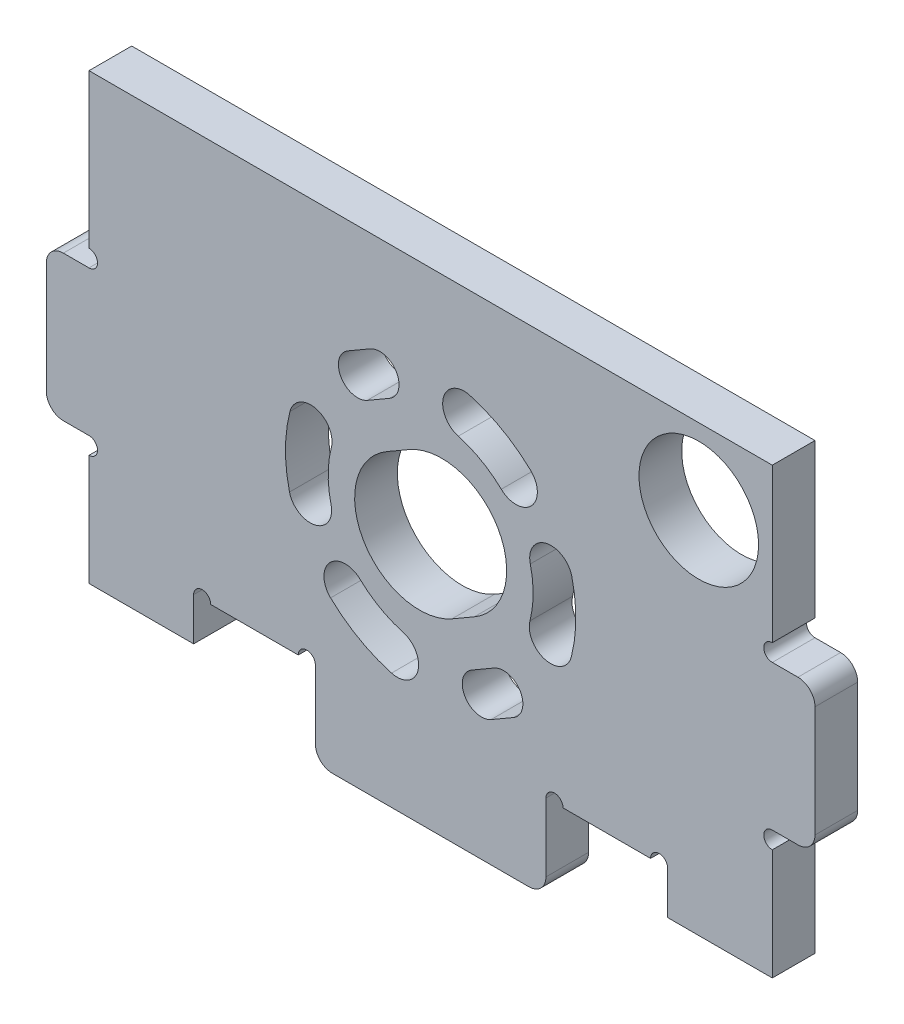
SolidWorks part; units mm, degrees
ref_plane "정면" through (0, 0, 0) normal (0, 0, 1) x (1, 0, 0)
ref_plane "윗면" through (0, 0, 0) normal (0, 1, 0) x (1, 0, 0)
ref_plane "우측면" through (0, 0, 0) normal (1, 0, 0) x (0, 0, -1)
sketch "스케치1" plane through (0, 0, 0) normal (0, 0, 1) x (1, 0, 0)
  line L0 (-3.8971, 23.25) -> (-1.299, 24.75) construction
  line L1 (-42.5981, 51) -> (37.4019, 51)
  line L2 (-42.5981, 51) -> (-42.5981, -1)
  line L3 (-42.5981, -1) -> (37.4019, -1)
  line L4 (37.4019, 51) -> (37.4019, -1)
  line L5 (-7.6971, 29.8318) -> (-5.099, 31.3318)
  line L6 (-0.0971, 16.6682) -> (2.501, 18.1682)
  line L7 (-9.8481, 36.5574) -> (-2.5981, 24) construction
  line L8 (-2.5981, 24) -> (4.6519, 11.4426) construction
  line L9 (-2.5981, 24) -> (4.6519, 36.5574) construction
  line L10 (-2.5981, 24) -> (11.9019, 24) construction
  line L11 (-2.5981, 24) -> (9.9593, 31.25) construction
  arc A0 (-7.6971, 29.8318) -> (-0.0971, 16.6682) centre (-3.8971, 23.25) ccw
  circle A1 centre (-2.5981, 24) radius 14.5 construction
  arc A2 (1.3092, 37.9636) -> (7.3956, 34.506) centre (-2.5981, 24) cw construction
  arc A3 (2.501, 18.1682) -> (-5.099, 31.3318) centre (-1.299, 24.75) ccw
  arc A4 (9.1187, 36.3174) -> (1.9829, 40.3712) centre (-2.5981, 24) ccw
  arc A5 (5.6726, 32.6946) -> (0.6355, 35.5561) centre (-2.5981, 24) ccw
  arc A6 (5.6726, 32.6946) -> (9.1187, 36.3174) centre (7.3956, 34.506) ccw
  arc A7 (1.9829, 40.3712) -> (0.6355, 35.5561) centre (1.3092, 37.9636) ccw
  arc A8 (11.4484, 20.402) -> (11.4972, 27.4018) centre (-2.5981, 24) ccw construction
  arc A9 (13.9275, 27.9883) -> (13.8702, 19.7816) centre (-2.5981, 24) cw
  arc A10 (9.067, 26.8153) -> (9.0266, 21.0223) centre (-2.5981, 24) cw
  arc A11 (9.067, 26.8153) -> (13.9275, 27.9883) centre (11.4972, 27.4018) cw
  arc A12 (13.8702, 19.7816) -> (9.0266, 21.0223) centre (11.4484, 20.402) cw
  arc A13 (-6.5053, 10.0364) -> (-12.5918, 13.494) centre (-2.5981, 24) cw construction
  arc A14 (-14.3148, 11.6826) -> (-7.179, 7.6288) centre (-2.5981, 24) ccw
  arc A15 (-10.8687, 15.3054) -> (-5.8317, 12.4439) centre (-2.5981, 24) ccw
  arc A16 (-10.8687, 15.3054) -> (-14.3148, 11.6826) centre (-12.5918, 13.494) ccw
  arc A17 (-7.179, 7.6288) -> (-5.8317, 12.4439) centre (-6.5053, 10.0364) ccw
  arc A18 (-16.6446, 27.598) -> (-16.6934, 20.5982) centre (-2.5981, 24) ccw construction
  arc A19 (-19.1236, 20.0117) -> (-19.0664, 28.2184) centre (-2.5981, 24) cw
  arc A20 (-14.2632, 21.1847) -> (-14.2228, 26.9777) centre (-2.5981, 24) cw
  arc A21 (-14.2632, 21.1847) -> (-19.1236, 20.0117) centre (-16.6934, 20.5982) cw
  arc A22 (-19.0664, 28.2184) -> (-14.2228, 26.9777) centre (-16.6446, 27.598) cw
  point P3 (-2.5981, 24)
  point P20 (4.5642, 36.6076)
  point P28 (11.9016, 23.8989)
  point P35 (-9.7603, 11.3924)
  point P42 (-17.0977, 24.1011)
  dimension "D1" = 30
  dimension "D2" = 40
  dimension "D8" = 7.6
  dimension "D5" = 29
  dimension "D11" = 2.5
  dimension "D3" = 80
  dimension "D4" = 52
  dimension "D6" = 60
  dimension "D7" = 3
  dimension "D9" = 25
  dimension "D10" = 60
  dimension "D12" = 7
extrude "보스-돌출1" add sketch "스케치1" along normal blind 5
sketch "스케치2" plane through (0, 0, 5) normal (0, 0, 1) x (1, 0, 0)
  line L0 (4.6519, 11.4426) -> (-2.5981, 24) construction
  line L1 (-2.5981, 24) -> (-9.8481, 36.5574) construction
  line L8 (5.2828, 28.55) -> (-2.5981, 24) construction
  line L9 (-2.5981, 24) -> (-10.4789, 19.45) construction
  line L10 (5.951, 12.1926) -> (3.3529, 10.6926) construction
  line L11 (7.076, 10.2441) -> (4.4779, 8.7441)
  line L12 (4.826, 14.1412) -> (2.2279, 12.6412)
  line L13 (-8.549, 37.3074) -> (-11.1471, 35.8074) construction
  line L14 (-7.424, 35.3588) -> (-10.0221, 33.8588)
  line L15 (-9.674, 39.2559) -> (-12.2721, 37.7559)
  arc A4 (2.501, 18.1682) -> (-5.099, 31.3318) centre (-1.299, 24.75) ccw construction
  arc A5 (-7.6971, 29.8318) -> (-0.0971, 16.6682) centre (-3.8971, 23.25) ccw construction
  arc A8 (7.076, 10.2441) -> (4.826, 14.1412) centre (5.951, 12.1926) ccw
  arc A9 (2.2279, 12.6412) -> (4.4779, 8.7441) centre (3.3529, 10.6926) ccw
  arc A10 (-7.424, 35.3588) -> (-9.674, 39.2559) centre (-8.549, 37.3074) ccw
  arc A11 (-12.2721, 37.7559) -> (-10.0221, 33.8588) centre (-11.1471, 35.8074) ccw
  point P28 (4.6519, 11.4426)
  point P34 (-9.8481, 36.5574)
  dimension "D2" = 3
  dimension "D3" = 2.25
  dimension "D4" = 2.25
  dimension "D1" = 29
extrude "컷-돌출1" cut sketch "스케치2" against normal blind 5
sketch "스케치3" plane through (0, 0, 5) normal (0, 0, 1) x (1, 0, 0)
  line L0 (-2.5981, 24) -> (28.7953, 42.125) construction
  line L1 (5.2828, 28.55) -> (-2.5981, 24) construction
  line L3 (-2.5981, 24) -> (-10.4789, 19.45) construction
  circle A0 centre (28.7953, 42.125) radius 7
  arc A1 (-7.6971, 29.8318) -> (-0.0971, 16.6682) centre (-3.8971, 23.25) ccw construction
  arc A2 (2.501, 18.1682) -> (-5.099, 31.3318) centre (-1.299, 24.75) ccw construction
  dimension "D2" = 14
  dimension "D1" = 36.25
extrude "컷-돌출2" cut sketch "스케치3" against normal blind 10
sketch "스케치4" plane through (0, 0, 5) normal (0, 0, 1) x (1, 0, 0)
  line L0 (5.2828, 28.55) -> (-2.5981, 24) construction
  line L1 (-2.5981, 24) -> (-10.4789, 19.45) construction
  circle A0 centre (-2.5981, 24) radius 7.5
  arc A5 (2.501, 18.1682) -> (-5.099, 31.3318) centre (-1.299, 24.75) ccw construction
  arc A6 (-7.6971, 29.8318) -> (-0.0971, 16.6682) centre (-3.8971, 23.25) ccw construction
sketch "스케치5" plane through (0, 0, 5) normal (0, 0, 1) x (1, 0, 0)
  line L0 (37.4019, -1) -> (37.4019, 51) construction
  line L1 (37.4019, 41) -> (42.4019, 41)
  line L2 (37.4019, 41) -> (37.4019, 31)
  line L3 (37.4019, 31) -> (42.4019, 31)
  line L4 (42.4019, 41) -> (42.4019, 31)
  line L5 (42.4019, 31) -> (42.4019, 19) construction
  line L6 (37.4019, 19) -> (42.4019, 19)
  line L7 (37.4019, 19) -> (37.4019, 9)
  line L8 (37.4019, 9) -> (42.4019, 9)
  line L9 (42.4019, 19) -> (42.4019, 9)
  line L10 (37.4019, 51) -> (-42.5981, 51) construction
  line L11 (-42.5981, -1) -> (37.4019, -1) construction
  line L12 (-2.5981, 51) -> (-2.5981, -1) construction
  line L13 (-47.5981, 19) -> (-47.5981, 9)
  line L14 (-42.5981, 9) -> (-47.5981, 9)
  line L15 (-42.5981, 19) -> (-42.5981, 9)
  line L16 (-42.5981, 19) -> (-47.5981, 19)
  line L17 (-47.5981, 41) -> (-47.5981, 31)
  line L18 (-42.5981, 31) -> (-47.5981, 31)
  line L19 (-42.5981, 41) -> (-42.5981, 31)
  line L20 (-42.5981, 41) -> (-47.5981, 41)
  dimension "D1" = 10
  dimension "D2" = 10
  dimension "D3" = 10
  dimension "D4" = 10
  dimension "D5" = 5
extrude "보스-돌출2" [suppressed] add sketch "스케치5" against normal blind 5
sketch "스케치6" [suppressed] plane through (0, 0, 5) normal (0, 0, 1) x (1, 0, 0)
  line L0 (27.4019, 41) -> (22.4019, 41) construction
  line L1 (22.4019, 31) -> (27.4019, 31) construction
  line L2 (27.4019, 19) -> (22.4019, 19) construction
  line L3 (22.4019, 9) -> (27.4019, 9) construction
  line L4 (-10.0981, 51) -> (-10.0981, -1) construction
  line L5 (22.4019, 51) -> (-42.5981, 51) construction
  line L6 (-42.5981, -1) -> (22.4019, -1) construction
  circle A0 centre (23.4019, 41) radius 1
  circle A1 centre (23.4019, 31) radius 1
  circle A2 centre (23.4019, 19) radius 1
  circle A3 centre (23.4019, 9) radius 1
  circle A4 centre (-43.5981, 9) radius 1
  circle A5 centre (-43.5981, 19) radius 1
  circle A6 centre (-43.5981, 31) radius 1
  circle A7 centre (-43.5981, 41) radius 1
  dimension "D1" = 2
extrude "컷-돌출3" [suppressed] cut sketch "스케치6" against normal blind 5
sketch "스케치8" plane through (0, 0, 5) normal (0, 0, 1) x (1, 0, 0)
  line L0 (-42.5981, 30.55) -> (-36.5981, 30.55)
  line L1 (-42.5981, 30.55) -> (-42.5981, 27.45)
  line L2 (-42.5981, 27.45) -> (-36.5981, 27.45)
  line L3 (-32.5981, 30.55) -> (-32.5981, 27.45) construction
  line L4 (-33.7981, 27.45) -> (-32.5981, 27.45)
  line L5 (-36.5981, 30.55) -> (-36.5981, 31.75)
  line L6 (-36.5981, 31.75) -> (-33.7981, 31.75) construction
  line L7 (-33.7981, 31.75) -> (-33.7981, 30.55)
  line L8 (-33.7981, 27.45) -> (-33.7981, 26.25)
  line L9 (-33.7981, 26.25) -> (-36.5981, 26.25) construction
  line L10 (-33.7981, 30.55) -> (-32.5981, 30.55)
  line L11 (-36.5981, 26.25) -> (-36.5981, 27.45)
  line L12 (-36.5981, 30.55) -> (-36.5981, 27.45) construction
  line L13 (-33.7981, 30.55) -> (-33.7981, 27.45) construction
  line L14 (-36.5981, 27.45) -> (-33.7981, 27.45) construction
  line L15 (-33.7981, 30.55) -> (-36.5981, 30.55) construction
  line L16 (-26.4709, 29) -> (-32.5981, 29) construction
  line L17 (-42.5981, 10.55) -> (-36.5981, 10.55)
  line L18 (-42.5981, 10.55) -> (-42.5981, 7.45)
  line L19 (-42.5981, 7.45) -> (-36.5981, 7.45)
  line L20 (-32.5981, 10.55) -> (-32.5981, 7.45) construction
  line L21 (-33.7981, 7.45) -> (-32.5981, 7.45)
  line L22 (-36.5981, 10.55) -> (-36.5981, 11.75)
  line L23 (-36.5981, 11.75) -> (-33.7981, 11.75) construction
  line L24 (-33.7981, 11.75) -> (-33.7981, 10.55)
  line L25 (-33.7981, 7.45) -> (-33.7981, 6.25)
  line L26 (-33.7981, 6.25) -> (-36.5981, 6.25) construction
  line L27 (-33.7981, 10.55) -> (-32.5981, 10.55)
  line L28 (-36.5981, 6.25) -> (-36.5981, 7.45)
  line L29 (-36.5981, 10.55) -> (-36.5981, 7.45) construction
  line L30 (-33.7981, 10.55) -> (-33.7981, 7.45) construction
  line L31 (-36.5981, 7.45) -> (-33.7981, 7.45) construction
  line L32 (-33.7981, 10.55) -> (-36.5981, 10.55) construction
  line L33 (-26.4709, 9) -> (-32.5981, 9) construction
  line L34 (-26.4709, 29) -> (-26.4709, 9) construction
  line L35 (-42.5981, -1) -> (37.4019, -1) construction
  line L36 (-2.5981, 51) -> (-2.5981, -1) construction
  line L37 (37.4019, 51) -> (-42.5981, 51) construction
  line L38 (21.2747, 29) -> (21.2747, 9) construction
  line L39 (21.2747, 9) -> (27.4019, 9) construction
  line L40 (28.6019, 10.55) -> (31.4019, 10.55) construction
  line L41 (31.4019, 7.45) -> (28.6019, 7.45) construction
  line L42 (28.6019, 10.55) -> (28.6019, 7.45) construction
  line L43 (31.4019, 10.55) -> (31.4019, 7.45) construction
  line L44 (28.6019, 6.25) -> (31.4019, 6.25) construction
  line L45 (31.4019, 11.75) -> (28.6019, 11.75) construction
  line L46 (27.4019, 10.55) -> (27.4019, 7.45) construction
  line L47 (21.2747, 29) -> (27.4019, 29) construction
  line L48 (28.6019, 30.55) -> (31.4019, 30.55) construction
  line L49 (31.4019, 27.45) -> (28.6019, 27.45) construction
  line L50 (28.6019, 30.55) -> (28.6019, 27.45) construction
  line L51 (31.4019, 30.55) -> (31.4019, 27.45) construction
  line L52 (28.6019, 26.25) -> (31.4019, 26.25) construction
  line L53 (31.4019, 31.75) -> (28.6019, 31.75) construction
  line L54 (27.4019, 30.55) -> (27.4019, 27.45) construction
  line L55 (31.4019, 6.25) -> (31.4019, 7.45)
  line L56 (28.6019, 10.55) -> (27.4019, 10.55)
  line L57 (28.6019, 7.45) -> (28.6019, 6.25)
  line L58 (28.6019, 11.75) -> (28.6019, 10.55)
  line L59 (31.4019, 10.55) -> (31.4019, 11.75)
  line L60 (28.6019, 7.45) -> (27.4019, 7.45)
  line L61 (37.4019, 7.45) -> (31.4019, 7.45)
  line L62 (37.4019, 10.55) -> (37.4019, 7.45)
  line L63 (37.4019, 10.55) -> (31.4019, 10.55)
  line L64 (31.4019, 26.25) -> (31.4019, 27.45)
  line L65 (28.6019, 30.55) -> (27.4019, 30.55)
  line L66 (28.6019, 27.45) -> (28.6019, 26.25)
  line L67 (28.6019, 31.75) -> (28.6019, 30.55)
  line L68 (31.4019, 30.55) -> (31.4019, 31.75)
  line L69 (28.6019, 27.45) -> (27.4019, 27.45)
  line L70 (37.4019, 27.45) -> (31.4019, 27.45)
  line L71 (37.4019, 30.55) -> (37.4019, 27.45)
  line L72 (37.4019, 30.55) -> (31.4019, 30.55)
  arc A0 (-33.7981, 31.75) -> (-36.5981, 31.75) centre (-35.1981, 31.75) ccw
  arc A1 (-36.5981, 26.25) -> (-33.7981, 26.25) centre (-35.1981, 26.25) ccw
  arc A2 (-32.5981, 27.45) -> (-32.5981, 30.55) centre (-32.5981, 29) ccw
  arc A3 (-33.7981, 11.75) -> (-36.5981, 11.75) centre (-35.1981, 11.75) ccw
  arc A4 (-36.5981, 6.25) -> (-33.7981, 6.25) centre (-35.1981, 6.25) ccw
  arc A5 (-32.5981, 7.45) -> (-32.5981, 10.55) centre (-32.5981, 9) ccw
  arc A6 (27.4019, 7.45) -> (27.4019, 10.55) centre (27.4019, 9) cw
  arc A7 (31.4019, 6.25) -> (28.6019, 6.25) centre (30.0019, 6.25) cw
  arc A8 (28.6019, 11.75) -> (31.4019, 11.75) centre (30.0019, 11.75) cw
  arc A9 (27.4019, 27.45) -> (27.4019, 30.55) centre (27.4019, 29) cw
  arc A10 (31.4019, 26.25) -> (28.6019, 26.25) centre (30.0019, 26.25) cw
  arc A11 (28.6019, 31.75) -> (31.4019, 31.75) centre (30.0019, 31.75) cw
  dimension "D1" = 3.1
  dimension "D2" = 10
  dimension "D3" = 5.5
  dimension "D4" = 2.8
  dimension "D5" = 3.1
  dimension "D6" = 10
  dimension "D7" = 5.5
  dimension "D8" = 2.8
  dimension "D9" = 20
  dimension "D10" = 10
extrude "컷-돌출4" [suppressed] cut sketch "스케치8" against normal blind 10
sketch "스케치10" plane through (0, 0, 5) normal (0, 0, 1) x (1, 0, 0)
  line L0 (10.9019, -6) -> (37.4019, -6) construction
  line L1 (-16.0981, -1) -> (10.9019, -1)
  line L2 (37.4019, -1) -> (37.4019, 51) construction
  line L3 (37.4019, 31) -> (42.4019, 31)
  line L4 (37.4019, 31) -> (37.4019, 14)
  line L5 (-16.0981, -1) -> (-16.0981, -6)
  line L6 (37.4019, 14) -> (42.4019, 14)
  line L7 (42.4019, 31) -> (42.4019, 14)
  line L8 (-42.5981, 51) -> (-42.5981, -1) construction
  line L9 (-42.5981, 31) -> (-47.5981, 31)
  line L10 (-42.5981, 31) -> (-42.5981, 14)
  line L11 (-16.0981, -6) -> (10.9019, -6)
  line L12 (-42.5981, 14) -> (-47.5981, 14)
  line L13 (-47.5981, 31) -> (-47.5981, 14)
  line L14 (37.4019, 51) -> (-42.5981, 51) construction
  line L15 (-42.5981, -1) -> (37.4019, -1) construction
  line L16 (10.9019, -1) -> (10.9019, -6)
  line L17 (37.4019, -6) -> (37.4019, -1) construction
  line L18 (-16.0981, -6) -> (-42.5981, -6) construction
  line L19 (-42.5981, -6) -> (-42.5981, -1) construction
  dimension "D1" = 5
  dimension "D2" = 20
  dimension "D3" = 15
  dimension "D4" = 27
  dimension "D5" = 5
extrude "보스-돌출3" add sketch "스케치10" against normal blind 5
sketch "스케치11" plane through (0, 0, 5) normal (0, 0, 1) x (1, 0, 0)
  line L0 (37.4019, 31) -> (37.4019, 51) construction
  line L1 (37.4019, -1) -> (37.4019, 14) construction
  line L2 (-42.5981, 14) -> (-42.5981, -1) construction
  line L3 (-42.5981, 51) -> (-42.5981, 31) construction
  line L4 (10.9019, -1) -> (37.4019, -1) construction
  line L5 (-42.5981, -1) -> (-16.0981, -1) construction
  circle A0 centre (37.4019, 32) radius 1
  circle A1 centre (37.4019, 13) radius 1
  circle A2 centre (-42.5981, 13) radius 1
  circle A3 centre (-42.5981, 32) radius 1
  circle A4 centre (11.9019, -1) radius 1
  circle A5 centre (-17.0981, -1) radius 1
  dimension "D1" = 2
extrude "컷-돌출5" cut sketch "스케치11" against normal blind 5
fillet "필렛1" radius 2 6 edges at (42.4019, 31, 2.5) (42.4019, 14, 2.5) (10.9019, -6, 2.5) (-16.0981, -6, 2.5) (-47.5981, 14, 2.5) (-47.5981, 31, 2.5)
sketch "스케치12" plane through (0, 0, 5) normal (0, 0, 1) x (1, 0, 0)
  line L0 (12.9019, -1) -> (37.4019, -1) construction
  line L1 (25.1519, -1) -> (10.9019, -1)
  line L2 (25.1519, -1) -> (25.1519, 4)
  line L3 (25.1519, 4) -> (10.9019, 4)
  line L4 (10.9019, -1) -> (10.9019, 4)
  line L5 (-42.5981, -1) -> (-18.0981, -1) construction
  line L6 (-30.3481, -1) -> (-16.0981, -1)
  line L7 (-30.3481, -1) -> (-30.3481, 4)
  line L8 (-30.3481, 4) -> (-16.0981, 4)
  line L9 (-16.0981, -1) -> (-16.0981, 4)
  line L10 (10.9019, -4) -> (10.9019, -1) construction
  dimension "D1" = 5
extrude "컷-돌출6" cut sketch "스케치12" against normal blind 10
sketch "스케치15" plane through (0, 0, 5) normal (0, 0, 1) x (1, 0, 0)
  line L0 (25.1519, 4) -> (10.9019, 4) construction
  line L1 (-16.0981, 4) -> (-30.3481, 4) construction
  circle A0 centre (11.9019, 4) radius 1
  circle A1 centre (24.1519, 4) radius 1
  circle A2 centre (-17.0981, 4) radius 1
  circle A3 centre (-29.3481, 4) radius 1
  dimension "D1" = 2
extrude "컷-돌출7" cut sketch "스케치15" against normal blind 10
